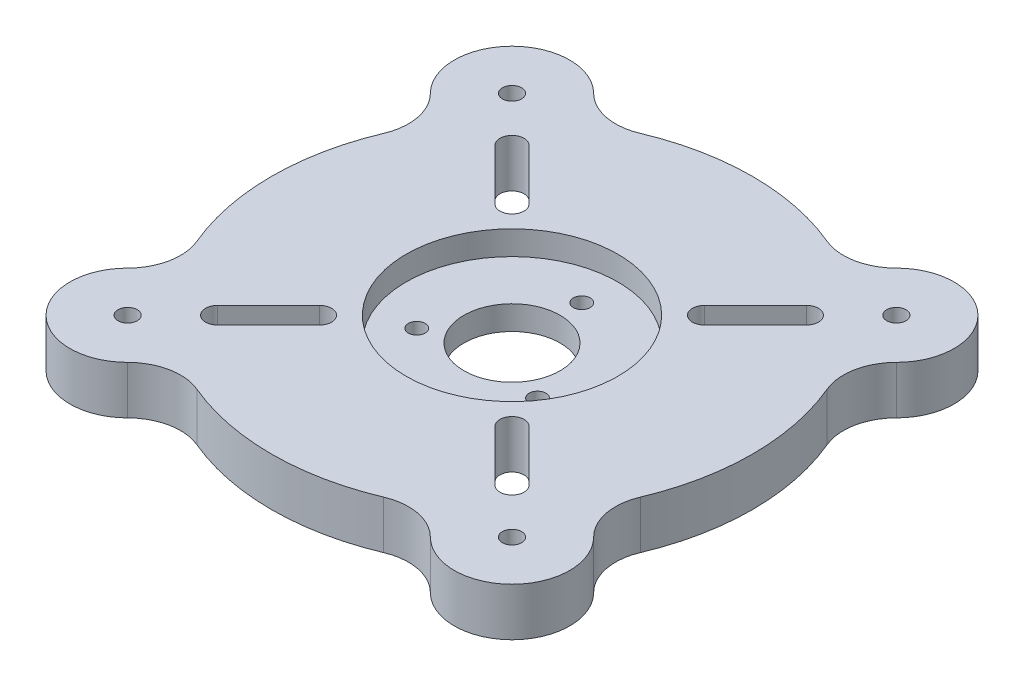
SolidWorks part; units mm, degrees
ref_plane "前视基准面" through (0, 0, 0) normal (0, 0, 1) x (1, 0, 0)
ref_plane "上视基准面" through (0, 0, 0) normal (0, 1, 0) x (1, 0, 0)
ref_plane "右视基准面" through (0, 0, 0) normal (1, 0, 0) x (0, 0, -1)
sketch "草图1" plane through (0, 0, 0) normal (0, 1, 0) x (1, 0, 0)
  line L0 (-39.9515, -39.9515) -> (39.9515, 39.9515) construction
  line L1 (-48.4368, -31.4663) -> (31.4663, 48.4368) construction
  line L2 (-31.4663, -48.4368) -> (48.4368, 31.4663) construction
  line L3 (0, 0) -> (0, 50) construction
  line L4 (39.9515, -39.9515) -> (-39.9515, 39.9515) construction
  line L5 (48.4368, -31.4663) -> (-31.4663, 48.4368) construction
  line L6 (31.4663, -48.4368) -> (-48.4368, 31.4663) construction
  line L7 (20, 20) -> (30.6066, 30.6066) construction
  line L8 (18.2322, 21.7678) -> (28.8388, 32.3744)
  line L9 (21.7678, 18.2322) -> (32.3744, 28.8388)
  line L10 (20, -20) -> (30.6066, -30.6066) construction
  line L11 (21.7678, -18.2322) -> (32.3744, -28.8388)
  line L12 (18.2322, -21.7678) -> (28.8388, -32.3744)
  line L13 (-20, -20) -> (-30.6066, -30.6066) construction
  line L14 (-18.2322, -21.7678) -> (-28.8388, -32.3744)
  line L15 (-21.7678, -18.2322) -> (-32.3744, -28.8388)
  line L16 (-20, 20) -> (-30.6066, 30.6066) construction
  line L17 (-21.7678, 18.2322) -> (-32.3744, 28.8388)
  line L18 (-18.2322, 21.7678) -> (-28.8388, 32.3744)
  circle A0 centre (0, 0) radius 50
  arc A1 (-48.4368, -31.4663) -> (-31.4663, -48.4368) centre (-39.9515, -39.9515) ccw construction
  arc A2 (48.4368, 31.4663) -> (31.4663, 48.4368) centre (39.9515, 39.9515) ccw construction
  arc A3 (48.4368, -31.4663) -> (31.4663, -48.4368) centre (39.9515, -39.9515) cw construction
  arc A4 (-48.4368, 31.4663) -> (-31.4663, 48.4368) centre (-39.9515, 39.9515) cw construction
  arc A5 (19.4135, 46.0773) -> (31.4663, 48.4368) centre (23.6858, 56.2173) ccw
  arc A6 (48.4368, 31.4663) -> (46.0773, 19.4135) centre (56.2173, 23.6858) ccw
  arc A7 (18.2322, 21.7678) -> (21.7678, 18.2322) centre (20, 20) ccw
  arc A8 (32.3744, 28.8388) -> (28.8388, 32.3744) centre (30.6066, 30.6066) ccw
  circle A9 centre (39.9515, 39.9515) radius 2
  arc A10 (31.4663, 48.4368) -> (48.4368, 31.4663) centre (39.9515, 39.9515) cw
  circle A11 centre (39.9515, -39.9515) radius 2
  arc A12 (48.4368, -31.4663) -> (31.4663, -48.4368) centre (39.9515, -39.9515) cw
  arc A13 (31.4663, -48.4368) -> (19.4135, -46.0773) centre (23.6858, -56.2173) ccw
  arc A14 (46.0773, -19.4135) -> (48.4368, -31.4663) centre (56.2173, -23.6858) ccw
  arc A15 (21.7678, -18.2322) -> (18.2322, -21.7678) centre (20, -20) ccw
  arc A16 (28.8388, -32.3744) -> (32.3744, -28.8388) centre (30.6066, -30.6066) ccw
  circle A17 centre (-39.9515, -39.9515) radius 2
  arc A18 (-31.4663, -48.4368) -> (-48.4368, -31.4663) centre (-39.9515, -39.9515) cw
  arc A19 (-48.4368, -31.4663) -> (-46.0773, -19.4135) centre (-56.2173, -23.6858) ccw
  arc A20 (-19.4135, -46.0773) -> (-31.4663, -48.4368) centre (-23.6858, -56.2173) ccw
  arc A21 (-18.2322, -21.7678) -> (-21.7678, -18.2322) centre (-20, -20) ccw
  arc A22 (-32.3744, -28.8388) -> (-28.8388, -32.3744) centre (-30.6066, -30.6066) ccw
  circle A23 centre (-39.9515, 39.9515) radius 2
  arc A24 (-48.4368, 31.4663) -> (-31.4663, 48.4368) centre (-39.9515, 39.9515) cw
  arc A25 (-31.4663, 48.4368) -> (-19.4135, 46.0773) centre (-23.6858, 56.2173) ccw
  arc A26 (-46.0773, 19.4135) -> (-48.4368, 31.4663) centre (-56.2173, 23.6858) ccw
  arc A27 (-21.7678, 18.2322) -> (-18.2322, 21.7678) centre (-20, 20) ccw
  arc A28 (-28.8388, 32.3744) -> (-32.3744, 28.8388) centre (-30.6066, 30.6066) ccw
  point P5 (0, 0)
  point P13 (0, 0)
  point P26 (25.3033, 25.3033)
  point P45 (25.3033, -25.3033)
  point P61 (-25.3033, -25.3033)
  point P77 (-25.3033, 25.3033)
  point P85 (0, 0)
  dimension "D1" = 100
  dimension "D2" = 12
  dimension "D5" = 2.5
  dimension "D8" = 4
  dimension "D3" = 113
  dimension "D4" = 45
  dimension "D6" = 15
  dimension "D7" = 20
  dimension "D10" = 18.2322
  dimension "D11" = 39.9515
  dimension "D12" = 18.2322
  dimension "D9" = 4
extrude "凸台-拉伸1" add sketch "草图1" along normal blind 10 contours A0 A28 L18 A27 L17 A22 L15 A21 L14 A16 L12 A15 L11 A8 L9 A7 L8 | A20 A0 A19 A18 A17 | A14 A0 A13 A12 A11 | A10 A5 A0 A6 A9 | A26 A0 A25 A24 A23 region at (0, 0, 0) region at (35.6807, 0, -35.6807) region at (44.9674, 0, 25.8881) region at (-35.6807, 0, -35.6807) region at (-25.8881, 0, 44.9674)
sketch "草图2" plane through (0, 10, 0) normal (0, 1, 0) x (1, 0, 0)
  circle A0 centre (0, 0) radius 22
  circle A1 centre (0, 14.5) radius 1.75
  circle A2 centre (12.5574, -7.25) radius 1.75
  circle A3 centre (-12.5574, -7.25) radius 1.75
  circle A4 centre (0, 0) radius 10
  point P12 (0, 0)
  dimension "D1" = 44
  dimension "D3" = 3.5
  dimension "D7" = 20
  dimension "D2" = 14.5
  dimension "D5" = 19.817
  dimension "D6" = 44.9317
  dimension "D4" = 3
extrude "切除-拉伸1" cut sketch "草图2" against normal blind 5 contours A0 A3 A2 A1 | A2 | A3 | A1 region at (-21.3777, 10, 0) region at (0, 10, -14.5) region at (12.5574, 10, 7.25) region at (-12.5574, 10, 7.25)
extrude "切除-拉伸2" cut sketch "草图2<3>" against normal through all contours A3 | A2 | A1 | A4 region at (0, 10, -14.5) region at (12.5574, 10, 7.25) region at (-12.5574, 10, 7.25) region at (0, 10, 0)
sketch "草图2<3>" plane through (0, 10, 0) normal (0, 1, 0) x (1, 0, 0) same geometry as "草图2"
